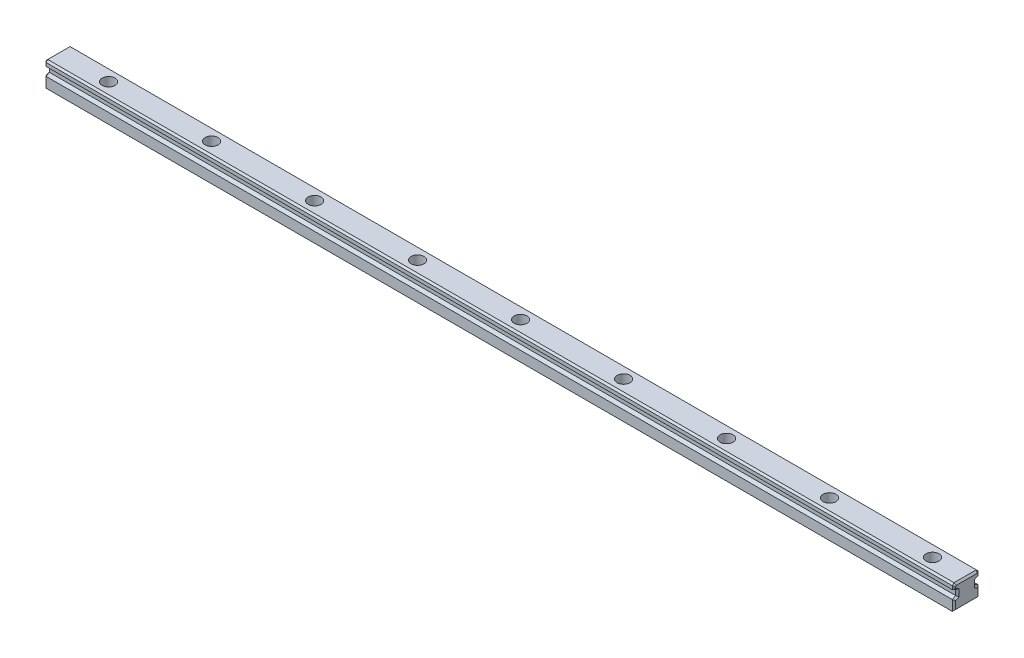
SolidWorks part; units mm, degrees
material "Chrome Stainless Steel"
ref_plane "Front Plane" through (0, 0, 0) normal (0, 0, 1) x (1, 0, 0)
ref_plane "Top Plane" through (0, 0, 0) normal (0, 1, 0) x (1, 0, 0)
ref_plane "Right Plane" through (0, 0, 0) normal (1, 0, 0) x (0, 0, -1)
sketch "Sketch1" plane through (0, 0, 0) normal (1, 0, 0) x (0, 0, -1)
  line L0 (0, 30.812) -> (0, -30.812) construction
  line L1 (-7.5, 0) -> (7.5, 0)
  line L2 (-6.5, 14) -> (6.5, 14)
  line L3 (-7.5, 14) -> (7.5, 14) construction
  line L4 (-6.5, 14) -> (-7.5, 13)
  line L5 (-7.5, 13) -> (-7.5, 11)
  line L6 (-7.5, 11) -> (-5.5, 10)
  line L7 (-5.5, 10) -> (-5.5, 7)
  line L8 (-5.5, 7) -> (-7.5, 6)
  line L9 (-7.5, 6) -> (-7.5, 0)
  line L10 (-7.5, 0) -> (7.5, 0) construction
  line L11 (7.5, 6) -> (7.5, 0)
  line L12 (5.5, 7) -> (7.5, 6)
  line L13 (5.5, 10) -> (5.5, 7)
  line L14 (7.5, 11) -> (5.5, 10)
  line L15 (7.5, 13) -> (7.5, 11)
  line L16 (6.5, 14) -> (7.5, 13)
  point P9 (0, 0)
  point P22 (0, 14)
  dimension "D3" = 1
  dimension "D4" = 1
  dimension "D5" = 7.5
  dimension "D6" = 2
  dimension "D7" = 1
  dimension "D8" = 2
  dimension "D9" = 3
  dimension "D10" = 6
  dimension "D2" = 14
extrude "Boss-Extrude1" add sketch "Sketch1" along normal blind 530
chamfer "Chamfer1" distance 1 angle 45 14 edges at (0, 0, 0) (0, 3, -7.5) (0, 6.5, -6.5) (0, 8.5, -5.5) (0, 10.5, -6.5) (0, 12, -7.5) (0, 13.5, -7) (0, 14, 0) (0, 13.5, 7) (0, 12, 7.5) (0, 10.5, 6.5) (0, 8.5, 5.5) (0, 6.5, 6.5) (0, 3, 7.5)
chamfer "Chamfer2" distance 1 angle 45 14 edges at (530, 6.5, 6.5) (530, 8.5, 5.5) (530, 10.5, 6.5) (530, 12, 7.5) (530, 13.5, 7) (530, 14, 0) (530, 13.5, -7) (530, 12, -7.5) (530, 10.5, -6.5) (530, 8.5, -5.5) (530, 6.5, -6.5) (530, 3, -7.5) (530, 0, 0) (530, 3, 7.5)
sketch "Sketch2" plane through (0, 14, 0) normal (0, 1, 0) x (1, 0, 0)
  line L0 (530, 6.0858) -> (530, -6.0858) construction
  circle A0 centre (510, 0) radius 3.75
  dimension "D2" = 7.5
  dimension "D1" = 20
extrude "Cut-Extrude1" cut sketch "Sketch2" against normal blind 5.3
sketch "Sketch3" plane through (0, 8.7, 0) normal (0, 1, 0) x (1, 0, 0)
  circle A0 centre (510, 0) radius 2.25
  dimension "D1" = 4.5
extrude "Cut-Extrude2" cut sketch "Sketch3" against normal through all
pattern_linear "LPattern1" count 67 spacing 60 along (-1, 0, 0) of "Cut-Extrude1", "Cut-Extrude2"
